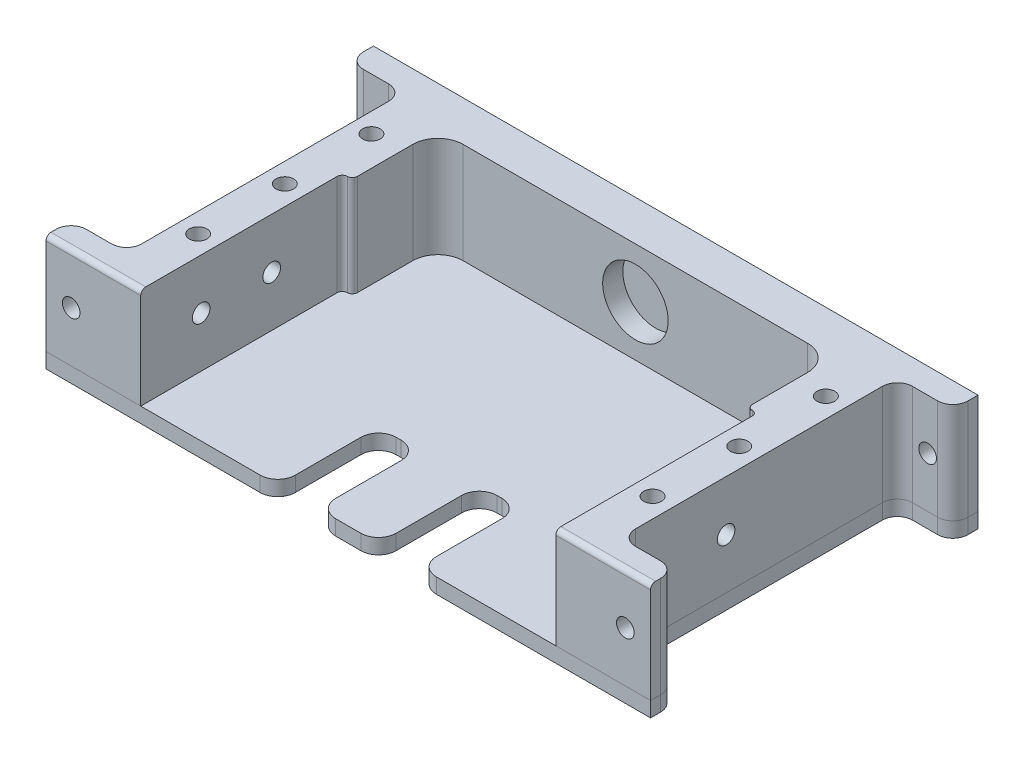
SolidWorks part; units mm, degrees
ref_plane "Plan de face" through (0, 0, 0) normal (0, 0, 1) x (1, 0, 0)
ref_plane "Plan de dessus" through (0, 0, 0) normal (0, 1, 0) x (1, 0, 0)
ref_plane "Plan de droite" through (0, 0, 0) normal (1, 0, 0) x (0, 0, -1)
sketch "Esquisse1" plane through (0, 0, 0) normal (0, 0, 1) x (1, 0, 0)
  line L0 (55, 0) -> (-55, 0) construction
  line L1 (60, -10) -> (-60, -10)
  line L2 (60, -10) -> (60, 10)
  line L3 (60, 10) -> (-60, 10)
  line L4 (-60, -10) -> (-60, 10)
  line L5 (60, -10) -> (-60, 10) construction
  line L6 (60, 10) -> (-60, -10) construction
  circle A0 centre (-55, 0) radius 1.75
  circle A1 centre (55, 0) radius 1.75
  point P0 (0, 0)
  point P9 (0, 0)
  dimension "D4" = 3.5
  dimension "D1" = 120
  dimension "D2" = 20
  dimension "D3" = 110
extrude "Boss.-Extru.1" add sketch "Esquisse1" along normal blind 65
sketch "Esquisse2" plane through (0, 10, 0) normal (0, 1, 0) x (1, 0, 0)
  line L0 (-60, -65) -> (-60, 0) construction
  line L1 (-41.2, -65) -> (-60, -65) construction
  line L2 (-41.2, -65) -> (-41.2, -60) construction
  line L3 (-41.2, -60) -> (-60, -60) construction
  line L4 (-60, -65) -> (-60, -60) construction
  line L5 (-41.2, -65) -> (-60, -60) construction
  line L6 (-41.2, -60) -> (-60, -65) construction
  line L7 (60, -65) -> (-60, -65) construction
  line L8 (60, 0) -> (-60, 0) construction
  line L9 (-41.2, -65) -> (-49, -65) construction
  line L10 (-41.2, -65) -> (-41.2, 0) construction
  line L11 (-41.2, 0) -> (-49, 0) construction
  line L12 (-49, -65) -> (-49, 0) construction
  line L13 (-41.2, -65) -> (-49, 0) construction
  line L14 (-41.2, 0) -> (-49, -65) construction
  line L15 (60, -32.5) -> (-60, -32.5) construction
  line L16 (0, -65) -> (0, 0) construction
  line L17 (-41.2, -5) -> (-60, -5) construction
  line L18 (41.2, -60) -> (60, -60) construction
  line L19 (49, -65) -> (49, 0) construction
  line L20 (41.2, -65) -> (41.2, 0) construction
  line L21 (41.2, -5) -> (60, -5) construction
  line L22 (-39.2, 0) -> (-39.2, -25) construction
  line L23 (-39.2, -25) -> (-41.2, -25) construction
  line L24 (39.2, -25) -> (41.2, -25) construction
  line L25 (39.2, 0) -> (39.2, -25) construction
  line L26 (-60, -8) -> (60, -8) construction
  line L27 (60, -65) -> (60, 0) construction
  line L29 (-60, -65) -> (-60, -60)
  line L30 (-60, -60) -> (-49, -60)
  line L31 (-49, -60) -> (-49, -5)
  line L32 (-49, -5) -> (-60, -5)
  line L33 (-60, -5) -> (-60, 0)
  line L34 (-60, 0) -> (60, 0)
  line L35 (60, 0) -> (60, -5)
  line L39 (60, -60) -> (60, -65)
  line L41 (-60, -65) -> (60, -65)
  line L42 (-41.2, -65) -> (-41.2, -25)
  line L43 (-41.2, -25) -> (-39.2, -25)
  line L44 (-39.2, -25) -> (-39.2, -8)
  line L45 (-39.2, -8) -> (39.2, -8)
  line L46 (39.2, -8) -> (39.2, -25)
  line L47 (39.2, -25) -> (41.2, -25)
  line L48 (41.2, -25) -> (41.2, -65)
  line L49 (60, -5) -> (49, -5)
  line L50 (49, -5) -> (49, -60)
  line L51 (49, -60) -> (60, -60)
  line L52 (-45.1, -32.5) -> (-45.1, -15.3) construction
  circle A0 centre (-45.1, -32.5) radius 1.75
  circle A1 centre (-45.1, -15.3) radius 1.75
  circle A2 centre (-45.1, -49.7) radius 1.75
  circle A3 centre (45.1, -15.3) radius 1.75
  circle A4 centre (45.1, -49.7) radius 1.75
  circle A5 centre (45.1, -32.5) radius 1.75
  point P0 (-50.6, -62.5)
  point P9 (-45.1, -32.5)
  point P19 (0, -32.5)
  point P23 (0, -32.5)
  line M15 (-60, 0) -> (-60, -65)
  line M17 (60, -65) -> (60, 0)
  dimension "D7" = 3.5
  dimension "D1" = 5
  dimension "D2" = 18.8
  dimension "D3" = 7.8
  dimension "D4" = 25
  dimension "D5" = 2
  dimension "D6" = 8
  dimension "D9" = 17.2
  dimension "D8" = 2
extrude "Enlèv. mat.-Extru.1" cut sketch "Esquisse2" against normal up to next contours L48 L47 L46 L45 L44 L43 L42 L41 | L31 L32 L30 M15 | L50 L51 L49 M17 | A1 | A2 | A0 | A3 | A5 | A4 region at (-54.5, 10, 32.5) region at (0, 10, 36.7938) region at (54.5, 10, 32.5) region at (-45.1, 10, 32.5) region at (-45.1, 10, 15.3) region at (-45.1, 10, 49.7) region at (45.1, 10, 15.3) region at (45.1, 10, 49.7) region at (45.1, 10, 32.5)
fillet "Congé1" radius 1 6 edges at (50.6, 10, 65) (-50.6, 10, 65) (-41.2, 0, 25) (-39.2, 0, 25) (41.2, 0, 25) (39.2, 0, 25)
fillet "Congé2" radius 5 2 edges at (-39.2, 0, 8) (39.2, 0, 8)
fillet "Congé3" radius 3 8 edges at (-60, 0, 60) (-49, 0, 60) (-60, 0, 5) (60, 0, 5) (49, 0, 60) (60, 0, 60) (49, 0, 5) (-49, 0, 5)
sketch "Esquisse5" plane through (49, 0, 0) normal (1, 0, 0) x (0, 0, -1)
  line L0 (-65, 0) -> (-53, 0) construction
  line L1 (-65, -10) -> (-65, 9) construction
  line L2 (-53, 0) -> (-39, 0) construction
  circle A0 centre (-53, 0) radius 1.75
  circle A1 centre (-39, 0) radius 1.75
  dimension "D1" = 3.5
  dimension "D2" = 12
  dimension "D3" = 14
  dimension "D4" = 2
extrude "Enlèv. mat.-Extru.2" cut sketch "Esquisse5" against normal up to surface (98 mm away) up to face at (-49, 0, 32.5)
sketch "Esquisse6" plane through (0, 0, 8) normal (0, 0, 1) x (1, 0, 0)
  circle A0 centre (0, 0) radius 6.5
  dimension "D1" = 13
extrude "Enlèv. mat.-Extru.3" cut sketch "Esquisse6" against normal blind 4
sketch "Esquisse7" plane through (0, -10, 0) normal (0, -1, 0) x (1, 0, 0)
  line L0 (6, 48.5) -> (6, 61.5)
  line L1 (-60, 0) -> (60, 0)
  line L2 (-60, 0) -> (-60, 65) construction
  line L3 (-60, 65) -> (60, 65) construction
  line L4 (60, 0) -> (60, 65) construction
  line L5 (14, 45) -> (-14, 45) construction
  line L6 (-60, 0) -> (60, 0) construction
  line L7 (-60, 2) -> (-60, 0) construction
  line L8 (60, 2) -> (60, 0) construction
  line L10 (-60, 0) -> (-60, 2)
  line L11 (-57, 5) -> (-52, 5)
  line L12 (-49, 8) -> (-49, 57)
  line L13 (-52, 60) -> (-57, 60)
  line L14 (-60, 63) -> (-60, 65)
  line L15 (-57, 5) -> (-52, 5) construction
  line L16 (-49, 8) -> (-49, 57) construction
  line L17 (-52, 60) -> (-57, 60) construction
  line L18 (0, 0) -> (0, 65) construction
  line L19 (60, 0) -> (60, 2)
  line L20 (57, 5) -> (52, 5)
  line L21 (49, 8) -> (49, 57)
  line L22 (60, 63) -> (60, 65)
  line L23 (52, 60) -> (57, 60)
  line L24 (14, 45) -> (14, 65) construction
  line L25 (14, 65) -> (-14, 65) construction
  line L26 (-14, 45) -> (-14, 65) construction
  line L27 (14, 45) -> (-14, 65) construction
  line L28 (14, 65) -> (-14, 45) construction
  line L29 (-9.5, 45) -> (-10.5, 45)
  line L30 (-6, 48.5) -> (-6, 61.5)
  line L31 (-6, 65) -> (-14, 65) construction
  line L32 (-14, 48.5) -> (-14, 61.5)
  line L33 (-6, 45) -> (-14, 65) construction
  line L34 (-6, 65) -> (-14, 45) construction
  line L35 (9.5, 45) -> (10.5, 45)
  line L36 (14, 48.5) -> (14, 61.5)
  line L37 (-60, 65) -> (-17.5, 65)
  line L38 (-2.5, 65) -> (2.5, 65)
  line L39 (17.5, 65) -> (60, 65)
  line L40 (-60, 65) -> (-41.2, 65) construction
  arc A0 (14, 61.5) -> (17.5, 65) centre (17.5, 61.5) cw
  arc A1 (52, 5) -> (49, 8) centre (52, 8) cw
  arc A2 (60, 2) -> (57, 5) centre (57, 2) ccw
  arc A3 (60, 63) -> (57, 60) centre (57, 63) cw
  arc A4 (49, 57) -> (52, 60) centre (52, 57) cw
  arc A5 (-49, 57) -> (-52, 60) centre (-52, 57) ccw
  arc A6 (-57, 60) -> (-60, 63) centre (-57, 63) cw
  arc A7 (-52, 5) -> (-49, 8) centre (-52, 8) ccw
  arc A8 (-60, 2) -> (-57, 5) centre (-57, 2) cw
  arc A9 (6, 61.5) -> (2.5, 65) centre (2.5, 61.5) ccw
  arc A10 (-6, 61.5) -> (-2.5, 65) centre (-2.5, 61.5) cw
  arc A11 (-17.5, 65) -> (-14, 61.5) centre (-17.5, 61.5) cw
  arc A12 (10.5, 45) -> (14, 48.5) centre (10.5, 48.5) ccw
  arc A13 (6, 48.5) -> (9.5, 45) centre (9.5, 48.5) ccw
  arc A14 (-9.5, 45) -> (-6, 48.5) centre (-9.5, 48.5) ccw
  arc A15 (-10.5, 45) -> (-14, 48.5) centre (-10.5, 48.5) cw
  point P22 (0, 55)
  point P25 (0, 32.5)
  point P33 (49, 5)
  point P36 (60, 5)
  point P39 (60, 60)
  point P42 (49, 60)
  point P45 (-49, 60)
  point P48 (-60, 60)
  point P51 (-49, 5)
  point P54 (-60, 5)
  point P59 (-10, 55)
  point P71 (6, 65)
  point P83 (6, 45)
  dimension "D1" = 3
  dimension "D5" = 3.5
  dimension "D2" = 8
  dimension "D3" = 28
  dimension "D4" = 20
extrude "Boss.-Extru.2" add sketch "Esquisse7" along normal blind 3 separate body
sketch "Esquisse8" plane through (0, -13, 0) normal (0, -1, 0) x (1, 0, 0)
  circle A0 centre (-45.1, 15.3) radius 1.75
  circle A2 centre (-45.1, 32.5) radius 1.75
  circle A3 centre (-45.1, 49.7) radius 1.75
  circle A4 centre (45.1, 49.7) radius 1.75
  circle A5 centre (45.1, 32.5) radius 1.75
  circle A6 centre (45.1, 15.3) radius 1.75
  circle A7 centre (45.1, 15.3) radius 1.75 construction
  circle A8 centre (45.1, 32.5) radius 1.75 construction
  circle A9 centre (45.1, 49.7) radius 1.75 construction
  circle A10 centre (-45.1, 49.7) radius 1.75 construction
  circle A11 centre (-45.1, 32.5) radius 1.75 construction
  circle A12 centre (-45.1, 15.3) radius 1.75 construction
extrude "Enlèv. mat.-Extru.4" cut sketch "Esquisse8" against normal up to next (3 mm away)
chamfer "Chanfrein1" distance 1.5 angle 45 4 edges at (-43.35, -13, 49.7) (-43.35, -13, 15.3) (46.85, -13, 49.7) (46.85, -13, 15.3)
